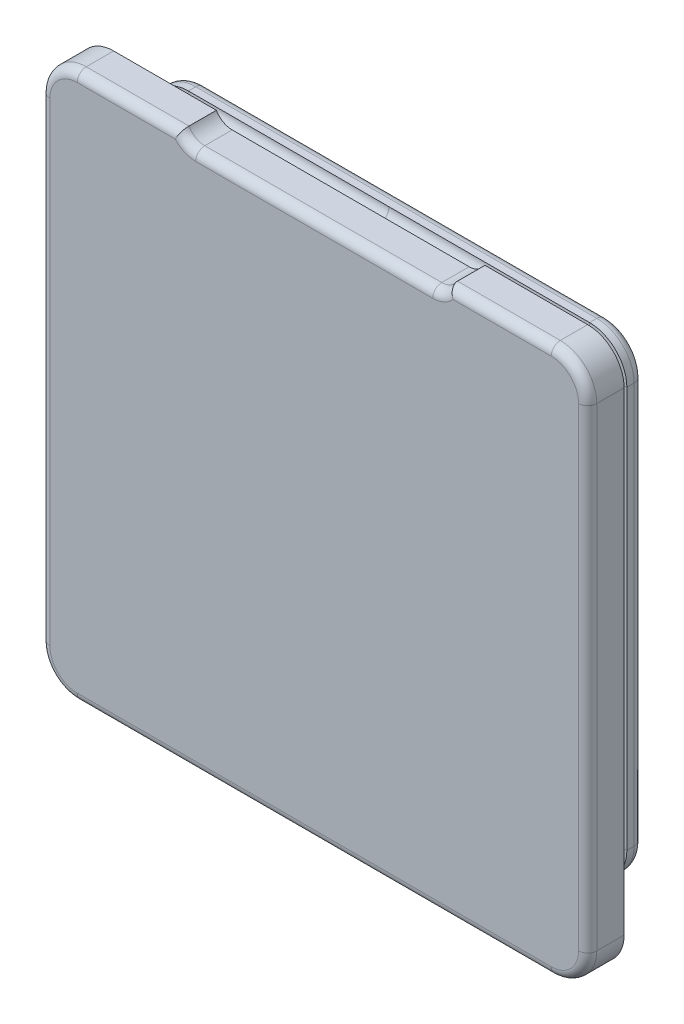
SolidWorks part; units mm, degrees
ref_plane "Front Plane" through (0, 0, 0) normal (0, 0, 1) x (1, 0, 0)
ref_plane "Top Plane" through (0, 0, 0) normal (0, 1, 0) x (1, 0, 0)
ref_plane "Right Plane" through (0, 0, 0) normal (1, 0, 0) x (0, 0, -1)
sketch "Sketch2" plane through (0, 0, 0) normal (0, 0, 1) x (1, 0, 0)
  line L0 (-65.4608, 99.5018) -> (-43.4608, 99.5018)
  line L18 (-67.8108, 134.0518) -> (-67.8108, 131.7518)
  line L19 (-67.3108, 131.2518) -> (-64.6108, 131.2518)
  line L20 (-64.1108, 130.7518) -> (-64.1108, 128.0518)
  line L21 (-64.6108, 127.5518) -> (-67.4608, 127.5518)
  line L22 (-69.4608, 125.5518) -> (-69.4608, 99.5518)
  line L23 (-67.4608, 97.5518) -> (-41.4608, 97.5518)
  line L24 (-39.4608, 99.5518) -> (-39.4608, 125.5518)
  line L25 (-41.4608, 127.5518) -> (-44.3108, 127.5518)
  line L26 (-44.8108, 128.0518) -> (-44.8108, 130.7518)
  line L27 (-44.3108, 131.2518) -> (-41.6108, 131.2518)
  line L28 (-41.1108, 131.7518) -> (-41.1108, 134.0518)
  line L34 (-67.8108, 134.0518) -> (-67.8108, 131.7518)
  line L35 (-67.3108, 131.2518) -> (-64.6108, 131.2518)
  line L36 (-64.1108, 130.7518) -> (-64.1108, 128.0518)
  line L37 (-64.6108, 127.5518) -> (-67.4608, 127.5518)
  line L38 (-69.4608, 125.5518) -> (-69.4608, 99.5518)
  line L39 (-67.4608, 97.5518) -> (-41.4608, 97.5518)
  line L40 (-39.4608, 99.5518) -> (-39.4608, 125.5518)
  line L41 (-41.4608, 127.5518) -> (-44.3108, 127.5518)
  line L42 (-44.8108, 128.0518) -> (-44.8108, 130.7518)
  line L43 (-44.3108, 131.2518) -> (-41.6108, 131.2518)
  line L44 (-41.1108, 131.7518) -> (-41.1108, 134.0518)
  line L48 (-67.5108, 101.5518) -> (-67.5108, 123.5518)
  line L50 (-41.4108, 123.5518) -> (-41.4108, 101.5518)
  line L51 (-65.4608, 125.6018) -> (-43.4608, 125.6018)
  line L59 (-64.6108, 127.5518) -> (-44.3108, 127.5518)
  line L69 (-61.9608, 134.5518) -> (-67.3108, 134.5518)
  line L70 (-61.9608, 134.5518) -> (-67.3108, 134.5518)
  line L71 (-61.9608, 128.0518) -> (-61.9608, 134.5518)
  line L72 (-61.9608, 128.0518) -> (-61.9608, 134.5518)
  line L73 (-46.9608, 133.8518) -> (-46.9608, 128.0518)
  line L74 (-46.9608, 133.8518) -> (-46.9608, 128.0518)
  line L75 (-47.9608, 127.0518) -> (-60.9608, 127.0518)
  line L76 (-47.9608, 127.0518) -> (-60.9608, 127.0518)
  line L80 (-41.1108, 134.0518) -> (-60.9608, 134.0518)
  line L81 (-41.1108, 134.0518) -> (-60.9608, 134.0518)
  line L248 (-60.9608, 133.8518) -> (-46.9608, 133.8518)
  line L249 (-60.9608, 133.8518) -> (-46.9608, 133.8518)
  line L359 (-60.9608, 134.0518) -> (-60.9608, 133.8518)
  line L360 (-60.9608, 134.0518) -> (-60.9608, 133.8518)
  arc A21 (-67.4608, 127.5518) -> (-69.4608, 125.5518) centre (-67.4608, 125.5518) ccw
  arc A22 (-69.4608, 99.5518) -> (-67.4608, 97.5518) centre (-67.4608, 99.5518) ccw
  arc A23 (-41.4608, 97.5518) -> (-39.4608, 99.5518) centre (-41.4608, 99.5518) ccw
  arc A24 (-39.4608, 125.5518) -> (-41.4608, 127.5518) centre (-41.4608, 125.5518) ccw
  arc A37 (-67.4608, 127.5518) -> (-69.4608, 125.5518) centre (-67.4608, 125.5518) ccw
  arc A38 (-69.4608, 99.5518) -> (-67.4608, 97.5518) centre (-67.4608, 99.5518) ccw
  arc A39 (-41.4608, 97.5518) -> (-39.4608, 99.5518) centre (-41.4608, 99.5518) ccw
  arc A40 (-39.4608, 125.5518) -> (-41.4608, 127.5518) centre (-41.4608, 125.5518) ccw
  arc A48 (-65.4608, 125.6018) -> (-67.5108, 123.5518) centre (-65.4608, 123.5518) ccw
  arc A49 (-67.5108, 101.5518) -> (-65.4608, 99.5018) centre (-65.4608, 101.5518) ccw
  arc A50 (-43.4608, 99.5018) -> (-41.4108, 101.5518) centre (-43.4608, 101.5518) ccw
  arc A51 (-41.4108, 123.5518) -> (-43.4608, 125.6018) centre (-43.4608, 123.5518) ccw
  arc A105 (-61.9608, 128.0518) -> (-60.9608, 127.0518) centre (-60.9608, 128.0518) ccw
  arc A106 (-61.9608, 128.0518) -> (-60.9608, 127.0518) centre (-60.9608, 128.0518) ccw
  arc A107 (-67.3108, 134.5518) -> (-67.8108, 134.0518) centre (-67.3108, 134.0518) ccw
  arc A108 (-67.3108, 134.5518) -> (-67.8108, 134.0518) centre (-67.3108, 134.0518) ccw
  arc A109 (-67.8108, 131.7518) -> (-67.3108, 131.2518) centre (-67.3108, 131.7518) ccw
  arc A110 (-67.8108, 131.7518) -> (-67.3108, 131.2518) centre (-67.3108, 131.7518) ccw
  arc A111 (-64.1108, 130.7518) -> (-64.6108, 131.2518) centre (-64.6108, 130.7518) ccw
  arc A112 (-64.1108, 130.7518) -> (-64.6108, 131.2518) centre (-64.6108, 130.7518) ccw
  arc A113 (-64.6108, 127.5518) -> (-64.1108, 128.0518) centre (-64.6108, 128.0518) ccw
  arc A114 (-64.6108, 127.5518) -> (-64.1108, 128.0518) centre (-64.6108, 128.0518) ccw
  arc A115 (-44.8108, 128.0518) -> (-44.3108, 127.5518) centre (-44.3108, 128.0518) ccw
  arc A116 (-44.8108, 128.0518) -> (-44.3108, 127.5518) centre (-44.3108, 128.0518) ccw
  arc A117 (-44.3108, 131.2518) -> (-44.8108, 130.7518) centre (-44.3108, 130.7518) ccw
  arc A118 (-44.3108, 131.2518) -> (-44.8108, 130.7518) centre (-44.3108, 130.7518) ccw
  arc A119 (-41.6108, 131.2518) -> (-41.1108, 131.7518) centre (-41.6108, 131.7518) ccw
  arc A120 (-41.6108, 131.2518) -> (-41.1108, 131.7518) centre (-41.6108, 131.7518) ccw
  arc A121 (-47.9608, 127.0518) -> (-46.9608, 128.0518) centre (-47.9608, 128.0518) ccw
  arc A122 (-47.9608, 127.0518) -> (-46.9608, 128.0518) centre (-47.9608, 128.0518) ccw
  dimension "D6" = 2.05
  dimension "D7" = 2.05
  dimension "D8" = 2.05
  dimension "D2" = 1.95
  dimension "D3" = 1.95
  dimension "D4" = 1.95
  dimension "D5" = 1.95
  dimension "D1" = 0
extrude "Boss-Extrude1" add sketch "Sketch2" against normal blind 2 contours L50 A51 L51 A48 L48 A49 A50 | L40 A40 L41 L59 L37 A37 L38 A38 L39 A39 A51 L50 A50 A49 L48 A48 L51 region at (-54.4608, 112.5518, 0) region at (-61.6729, 126.8184, 0)
extrude "Boss-Extrude2" add sketch "Sketch2<2>" against normal blind 5 contours L50 A51 L51 A48 L48 A49 A50 region at (-54.4608, 112.5518, 0)
sketch "Sketch2<2>" plane through (0, 0, 0) normal (0, 0, 1) x (1, 0, 0) same geometry as "Sketch2"
sketch "Sketch6" plane through (0, 0, -5) normal (0, 0, -1) x (-1, 0, 0)
  line L4 (44.4108, 102.5018) -> (64.5108, 102.5018)
  line L5 (44.4108, 102.5018) -> (64.5108, 102.5018)
  line L12 (44.4108, 122.6018) -> (44.4108, 102.5018)
  line L13 (44.4108, 122.6018) -> (44.4108, 102.5018)
  line L16 (64.5108, 102.5018) -> (64.5108, 122.6018)
  line L17 (64.5108, 102.5018) -> (64.5108, 122.6018)
  line L18 (64.5108, 122.6018) -> (44.4108, 122.6018)
  line L19 (64.5108, 122.6018) -> (44.4108, 122.6018)
  dimension "D1" = 3
extrude "Cut-Extrude1" cut sketch "Sketch6" against normal up to surface (3 mm away) up to face at (-54.4608, 117.4491, -2)
ref_plane "Plane1" through (0, 0, -3.5) normal (0, 0, 1) x (1, 0, 0)
ref_plane "Plane2" through (-54.4608, 0, 0) normal (1, 0, 0) x (0, 0, -1)
sketch "Sketch4" plane through (0, 0, -3.5) normal (0, 0, 1) x (1, 0, 0)
  line L4 (-41.4108, 101.5518) -> (-41.4108, 123.5518)
  line L5 (-65.4608, 99.5018) -> (-43.4608, 99.5018)
  line L6 (-67.5108, 123.5518) -> (-67.5108, 101.5518)
  line L7 (-43.4608, 125.6018) -> (-65.4608, 125.6018)
  line L8 (-41.4108, 101.5518) -> (-41.4108, 123.5518)
  line L9 (-65.4608, 99.5018) -> (-43.4608, 99.5018)
  line L10 (-67.5108, 123.5518) -> (-67.5108, 101.5518)
  line L11 (-43.4608, 125.6018) -> (-65.4608, 125.6018)
  arc A4 (-43.4608, 99.5018) -> (-41.4108, 101.5518) centre (-43.4608, 101.5518) ccw
  arc A5 (-67.5108, 101.5518) -> (-65.4608, 99.5018) centre (-65.4608, 101.5518) ccw
  arc A6 (-65.4608, 125.6018) -> (-67.5108, 123.5518) centre (-65.4608, 123.5518) ccw
  arc A7 (-41.4108, 123.5518) -> (-43.4608, 125.6018) centre (-43.4608, 123.5518) ccw
  arc A8 (-43.4608, 99.5018) -> (-41.4108, 101.5518) centre (-43.4608, 101.5518) ccw
  arc A9 (-67.5108, 101.5518) -> (-65.4608, 99.5018) centre (-65.4608, 101.5518) ccw
  arc A10 (-65.4608, 125.6018) -> (-67.5108, 123.5518) centre (-65.4608, 123.5518) ccw
  arc A11 (-41.4108, 123.5518) -> (-43.4608, 125.6018) centre (-43.4608, 123.5518) ccw
  dimension "D1" = 0
sketch "Sketch5" plane through (-54.4608, 0, 0) normal (1, 0, 0) x (0, 0, -1)
  circle A0 centre (3.5, 125.6018) radius 0.6
  dimension "D1" = 1.2
sweep "Cut-Sweep1" cut profiles "Sketch5" path "Sketch4"
fillet "Fillet1" radius 0.5 28 edges at (-44.2777, 127.5518, 0) (-40.0465, 126.966, 0) (-39.4608, 112.5518, 0) (-40.0465, 98.1376, 0) (-54.4608, 97.5518, 0) (-68.875, 98.1376, 0) (-69.4608, 112.5518, 0) (-68.875, 126.966, 0) (-64.6438, 127.5518, 0) (-61.4608, 127.1858, 0) (-54.4608, 127.0518, 0) (-47.4608, 127.1858, 0) (-64.5108, 112.5518, -2) (-54.4608, 102.5018, -2) (-44.4108, 112.5518, -2) (-54.4608, 122.6018, -2) (-42.0112, 125.0014, -5) (-54.4608, 125.6018, -5) (-66.9103, 125.0014, -5) (-67.5108, 112.5518, -5) (-66.9103, 100.1022, -5) (-54.4608, 99.5018, -5) (-42.0112, 100.1022, -5) (-41.4108, 112.5518, -5) (-64.5108, 112.5518, -5) (-54.4608, 122.6018, -5) (-44.4108, 112.5518, -5) (-54.4608, 102.5018, -5)
